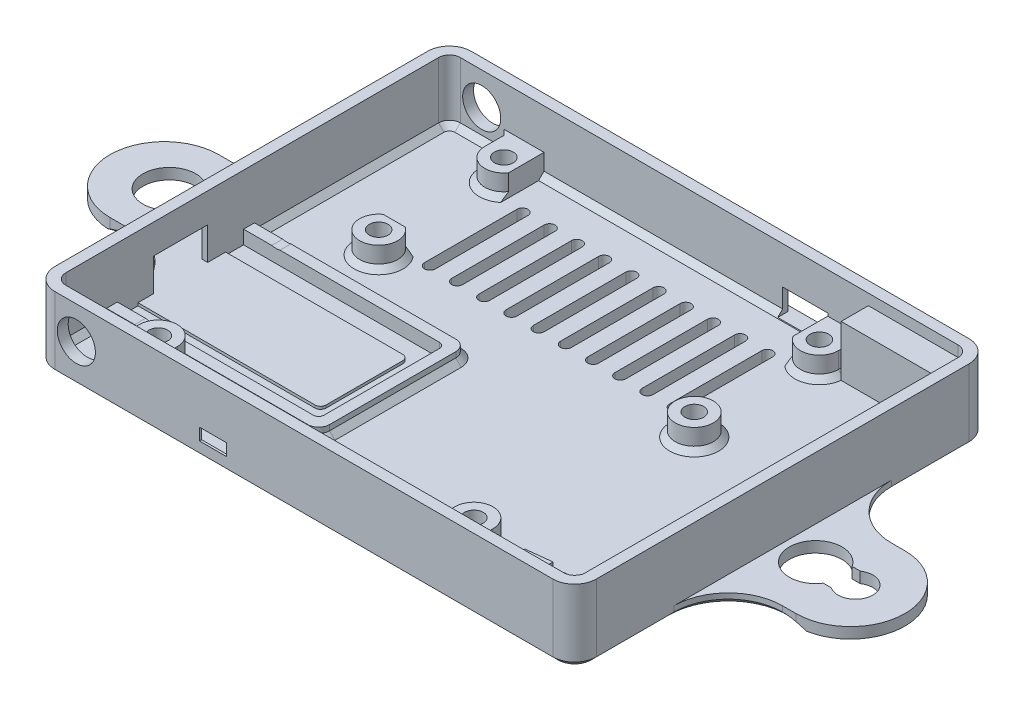
SolidWorks part; units mm, degrees
note: The reader was unsure of these and kept them because the rebuilt part matched: shared geometry of "Sketch2<3>".
ref_plane "Front Plane" through (0, 0, 0) normal (0, 0, 1) x (1, 0, 0)
ref_plane "Top Plane" through (0, 0, 0) normal (0, 1, 0) x (1, 0, 0)
ref_plane "Right Plane" through (0, 0, 0) normal (1, 0, 0) x (0, 0, -1)
sketch "Sketch1" plane through (0, 0, 0) normal (0, 1, 0) x (1, 0, 0)
  line L0 (-65.617, -16.3721) -> (-0.617, -16.3721)
  line L1 (-62.117, 10.1279) -> (-4.117, 10.1279)
  line L2 (-62.117, 10.1279) -> (-62.117, -12.8721)
  line L3 (-65.617, 13.6279) -> (-0.617, 13.6279)
  line L4 (-65.617, 13.6279) -> (-65.617, -16.3721)
  line L5 (-62.117, -12.8721) -> (-4.117, -12.8721)
  line L6 (-0.617, 13.6279) -> (-0.617, -16.3721)
  line L7 (-4.117, 10.1279) -> (-4.117, -12.8721)
  line L8 (-24.217, 16.7282) -> (-24.217, 15.4455)
  line L9 (-11.617, 16.7282) -> (-11.617, 15.4455)
  dimension "D1" = 65
  dimension "D2" = 30
  dimension "D3" = 58
  dimension "D4" = 23
  dimension "D5" = 3.5
  dimension "D6" = 3.5
sketch "Sketch2" plane through (0, 0, 0) normal (0, 1, 0) x (1, 0, 0)
  line L0 (-0.617, 13.6279) -> (-0.617, -16.3721) construction
  line L1 (32.4749, -18.9645) -> (30.9945, -18.9645)
  line L2 (32.4749, -24.2798) -> (30.9945, -24.2798)
  line L3 (33.3493, -21.6221) -> (26.04, -21.6221)
  line L4 (-85.4447, -21.6221) -> (-92.754, -21.6221)
  line L5 (-86.3191, -18.9645) -> (-87.7995, -18.9645)
  line L6 (-76.617, 13.6279) -> (-76.617, -16.3721)
  line L7 (-76.617, 12.6279) -> (-76.617, -55.8721)
  line L8 (-86.3191, -24.2798) -> (-87.7995, -24.2798)
  line L9 (-88.617, -11.6221) -> (-92.754, -11.6221)
  line L10 (-74.617, -57.8721) -> (16.883, -57.8721)
  line L11 (-78.617, -41.6221) -> (-78.617, -55.8721)
  line L12 (-88.617, -31.6221) -> (-92.754, -31.6221)
  line L13 (-85.4447, -11.6221) -> (-92.754, -11.6221) construction
  line L14 (18.883, 12.6279) -> (18.883, -55.8721)
  line L15 (-74.617, 14.6279) -> (16.883, 14.6279)
  line L16 (-74.617, -59.8721) -> (16.883, -59.8721)
  line L17 (20.883, 12.6279) -> (20.883, -1.6221)
  line L18 (-74.617, 16.6279) -> (16.883, 16.6279)
  line L19 (-85.4447, -31.6221) -> (-92.754, -31.6221) construction
  line L20 (33.3493, -11.6221) -> (30.883, -11.6221)
  line L21 (33.3493, -31.6221) -> (30.883, -31.6221)
  line L22 (33.3493, -11.6221) -> (26.04, -11.6221) construction
  line L23 (33.3493, -31.6221) -> (26.04, -31.6221) construction
  line L24 (-78.617, 12.6279) -> (-78.617, -55.8721) construction
  line L25 (-78.617, 12.6279) -> (-78.617, -1.6221)
  line L26 (20.883, 12.6279) -> (20.883, -55.8721) construction
  line L27 (20.883, -41.6221) -> (20.883, -55.8721)
  arc A0 (-74.617, -57.8721) -> (-76.617, -55.8721) centre (-74.617, -55.8721) cw
  arc A1 (16.883, -57.8721) -> (18.883, -55.8721) centre (16.883, -55.8721) ccw
  arc A2 (18.883, 12.6279) -> (16.883, 14.6279) centre (16.883, 12.6279) ccw
  arc A3 (-74.617, 14.6279) -> (-76.617, 12.6279) centre (-74.617, 12.6279) ccw
  arc A4 (-74.617, -59.8721) -> (-78.617, -55.8721) centre (-74.617, -55.8721) cw
  arc A5 (16.883, -59.8721) -> (20.883, -55.8721) centre (16.883, -55.8721) ccw
  arc A6 (20.883, 12.6279) -> (16.883, 16.6279) centre (16.883, 12.6279) ccw
  arc A7 (-74.617, 16.6279) -> (-78.617, 12.6279) centre (-74.617, 12.6279) ccw
  arc A8 (30.9945, -18.9645) -> (30.9945, -24.2798) centre (26.9479, -21.6221) ccw
  arc A9 (32.4749, -24.2798) -> (32.4749, -18.9645) centre (34.2572, -21.6221) ccw
  arc A10 (-86.3191, -24.2798) -> (-86.3191, -18.9645) centre (-84.5368, -21.6221) ccw
  arc A11 (-87.7995, -18.9645) -> (-87.7995, -24.2798) centre (-91.8461, -21.6221) ccw
  arc A12 (-92.754, -11.6221) -> (-92.754, -31.6221) centre (-92.754, -21.6221) ccw
  arc A13 (33.3493, -11.6221) -> (33.3493, -31.6221) centre (33.3493, -21.6221) cw
  arc A14 (-78.617, -41.6221) -> (-88.617, -31.6221) centre (-88.617, -41.6221) ccw
  arc A15 (-88.617, -11.6221) -> (-78.617, -1.6221) centre (-88.617, -1.6221) ccw
  arc A16 (20.883, -1.6221) -> (30.883, -11.6221) centre (30.883, -1.6221) ccw
  arc A17 (30.883, -31.6221) -> (20.883, -41.6221) centre (30.883, -41.6221) ccw
  point P62 (-78.617, -11.6221)
  point P67 (20.883, -31.6221)
  dimension "D4" = 2
  dimension "D10" = 10
  dimension "D11" = 10
  dimension "D12" = 10
  dimension "D13" = 10
  dimension "D3" = 72.5
  dimension "D2" = 19.5
  dimension "D1" = 11
  dimension "D5" = 2
  dimension "D6" = 10
  dimension "D7" = 10
  dimension "D8" = 10
  dimension "D9" = 10
extrude "Boss-Extrude1" add sketch "Sketch2" along normal blind 13.4 contours A17 L21 A13 L20 A16 L17 A6 L18 A7 L25 A15 L9 A12 L12 A14 L11 A4 L16 A5 L27 A11 L5 A10 L8 A9 L2 A8 L1 A3 L15 A2 L14 A1 L10 A0 L7
sketch "Sketch23" plane through (0, 13.4, 0) normal (0, 1, 0) x (1, 0, 0)
  line L1 (-78.617, -1.6221) -> (-103.7829, -1.6221)
  line L2 (-78.617, -1.6221) -> (-78.617, -41.6221)
  line L3 (-78.617, -41.6221) -> (-103.7829, -41.6221)
  line L4 (-103.7829, -1.6221) -> (-103.7829, -41.6221)
  line L5 (20.883, -1.6221) -> (47.1562, -1.6221)
  line L6 (20.883, -1.6221) -> (20.883, -41.6221)
  line L7 (20.883, -41.6221) -> (47.1562, -41.6221)
  line L8 (47.1562, -1.6221) -> (47.1562, -41.6221)
extrude "Cut-Extrude9" cut sketch "Sketch23" against normal offset from surface (11.4 mm away) 2 up to face at (-29.0341, 0, 21.6221)
extrude "Boss-Extrude2" add sketch "Sketch2<3>" along normal blind 2 contours L15 A3 L7 A0 L10 A1 L14 A2
sketch "Sketch2<3>" plane through (0, 0, 0) normal (0, 1, 0) x (1, 0, 0) same geometry as "Sketch2"
sketch "Sketch4" plane through (0, 2, 0) normal (0, 1, 0) x (1, 0, 0)
  line L0 (-59.2343, 14.6279) -> (-59.2343, 8.1428)
  line L5 (-7.0825, 14.6279) -> (-0.617, 14.6279)
  line L6 (-0.617, 10.1279) -> (-0.617, 14.6279)
  line L9 (-64.1397, -10.0158) -> (-60.0943, -10.0158)
  line L10 (-59.2343, 14.6279) -> (-65.617, 14.6279)
  line L11 (-65.617, 14.6279) -> (-65.617, 10.1279)
  line L12 (-7.0825, 14.6279) -> (-7.0825, 8.269)
  arc A1 (-7.0825, 8.269) -> (-0.617, 10.1279) centre (-4.117, 10.1279) ccw
  arc A2 (-64.1397, -10.0158) -> (-60.0943, -10.0158) centre (-62.117, -12.8721) ccw
  arc A3 (-65.617, 10.1279) -> (-59.2343, 8.1428) centre (-62.117, 10.1279) ccw
  circle A5 centre (-4.117, -12.8721) radius 3.5
extrude "Boss-Extrude3" add sketch "Sketch4" along normal offset from surface (4 mm away) 7.4 up to face at (-28.867, 13.4, 21.6221)
hole_wizard "CSK for #4 Flat Head Socket Cap Screw1" positions "Sketch6" profile "Sketch5" countersink size "#4" standard "ANSI Inch" end condition through all
sketch "Sketch6" plane through (0, 0, 0) normal (0, -1, 0) x (-1, 0, 0)
  point P0 (4.117, 10.1279)
  point P4 (62.117, 10.1279)
  point P8 (4.117, -12.8721)
  point P12 (62.117, -12.8721)
sketch "Sketch5" plane through (-4.117, 0, -10.1279) normal (1, 0, 0) x (0, 0, -1)
  line L0 (0, 0) -> (0, 13.4)
  line L1 (0, 13.4) -> (1.7272, 13.4)
  line L2 (1.7272, 13.4) -> (1.7272, 1.8805)
  line L3 (1.7272, 1.8805) -> (3.3619, 0)
  line L5 (3.3619, 0) -> (0, 0)
  line L6 (-1.7272, 1.8805) -> (-3.3619, 0) construction
  line L11 (0, -6.35) -> (0, 107.95) construction
  dimension "Thru Hole Dia." = 3.4544
  dimension "Thru Hole Depth" = 13.4
  dimension "Near C'Sink Dia." = 6.7237
  dimension "Near C'Sink Angle" = 82
sketch "Sketch7" plane through (0, 0, -16.6279) normal (0, 0, -1) x (-1, 0, 0)
  line L0 (11.2325, 6.5) -> (11.2325, 2.1) construction
  line L1 (7.0825, 6.5) -> (15.3825, 6.5)
  line L2 (7.0825, 6.5) -> (7.0825, 2.1)
  line L3 (7.0825, 2.1) -> (15.3825, 2.1)
  line L4 (15.3825, 6.5) -> (15.3825, 2.1)
  line L5 (0.617, 6) -> (7.0825, 6) construction
  dimension "D1" = 8.3
  dimension "D2" = 0.5
  dimension "D4" = 4.4
extrude "Cut-Extrude1" cut sketch "Sketch7" against normal up to next
sketch "Sketch15" plane through (0, 2, 0) normal (0, 1, 0) x (1, 0, 0)
  line L1 (-76.617, -23.2053) -> (-39.617, -23.2053)
  line L2 (-76.617, -21.2053) -> (-76.617, -23.2053)
  line L3 (-76.617, -46.4053) -> (-39.617, -46.4053)
  line L4 (-39.617, -23.2053) -> (-39.617, -46.4053)
  line L5 (-76.617, -21.2053) -> (-37.617, -21.2053)
  line L6 (-37.617, -21.2053) -> (-37.617, -48.4053)
  line L7 (-76.617, -48.4053) -> (-37.617, -48.4053)
  line L8 (-76.617, -46.4053) -> (-76.617, -48.4053)
  dimension "D1" = 23.2
extrude "Boss-Extrude5" add sketch "Sketch15" along normal blind 2
fillet "Fillet1" radius 1 1 edges at (-39.617, 3, 23.2053)
fillet "Fillet2" radius 1 1 edges at (-39.617, 3, 46.4053)
fillet "Fillet3" radius 2 2 edges at (-37.617, 3, 48.4053) (-37.617, 3, 21.2053)
sketch "Sketch16" plane through (-76.617, 0, 0) normal (1, 0, 0) x (0, 0, -1)
  line L1 (-39.8053, 2) -> (-29.8053, 2)
  line L2 (-39.8053, 2) -> (-39.8053, 8)
  line L3 (-39.8053, 8) -> (-29.8053, 8)
  line L4 (-29.8053, 2) -> (-29.8053, 8)
  dimension "D1" = 6
  dimension "D2" = 10
extrude "Cut-Extrude4" cut sketch "Sketch16" against normal up to next
sketch "Sketch9" plane through (0, 2, 0) normal (0, 1, 0) x (1, 0, 0)
  line L2 (-65.617, -57.8721) -> (-58.617, -57.8721)
  line L3 (-58.617, -53.3721) -> (-58.617, -57.8721)
  line L4 (-7.617, -53.3721) -> (-7.617, -57.8721)
  line L5 (-74.617, -57.8721) -> (16.883, -57.8721) construction
  line L6 (-65.617, -53.3721) -> (-65.617, -57.8721)
  line L7 (-7.617, -57.8721) -> (-0.617, -57.8721)
  line L8 (-0.617, -53.3721) -> (-0.617, -57.8721)
  arc A0 (-0.617, -53.3721) -> (-7.617, -53.3721) centre (-4.117, -53.3721) ccw
  arc A1 (-58.617, -53.3721) -> (-65.617, -53.3721) centre (-62.117, -53.3721) ccw
extrude "Boss-Extrude4" add sketch "Sketch9" along normal offset from surface (7.4 mm away) 4 up to face at (-28.867, 13.4, 21.6221)
hole_wizard "CSK for #4 Flat Head Socket Cap Screw2" positions "Sketch11" profile "Sketch10" countersink size "#4" standard "ANSI Inch" end condition through all
sketch "Sketch11" plane through (0, 0, 0) normal (0, -1, 0) x (-1, 0, 0)
  point P0 (4.117, -53.3721)
  point P9 (62.117, -53.3721)
sketch "Sketch10" plane through (-4.117, 0, 53.3721) normal (1, 0, 0) x (0, 0, -1)
  line L0 (0, 0) -> (0, 13.4)
  line L1 (0, 13.4) -> (1.7272, 13.4)
  line L2 (1.7272, 13.4) -> (1.7272, 1.8805)
  line L3 (1.7272, 1.8805) -> (3.3619, 0)
  line L5 (3.3619, 0) -> (0, 0)
  line L6 (-1.7272, 1.8805) -> (-3.3619, 0) construction
  line L11 (0, -6.35) -> (0, 107.95) construction
  dimension "Thru Hole Dia." = 3.4544
  dimension "Thru Hole Depth" = 13.4
  dimension "Near C'Sink Dia." = 6.7237
  dimension "Near C'Sink Angle" = 82
chamfer "Chamfer1" distance 1 angle 45 6 edges at (-65.617, 4, -14.6279) (-65.617, 5.7, 57.8721) (-58.617, 5.7, 57.8721) (-0.617, 4, -14.6279) (-0.617, 5.7, 57.8721) (-7.617, 5.7, 57.8721)
chamfer "Chamfer2" distance 1 angle 45 30 edges at (-62.117, 2, 16.3721) (-65.617, 2, -11.8779) (-63.1564, 2, -6.7858) (18.883, 2, 21.6221) (-70.617, 2, -14.6279) (-76.0312, 2, -14.0421) (-76.617, 2, 4.2887) (-33.1584, 2, -14.6279) (-70.617, 2, 57.8721) (-76.0312, 2, 57.2864) (-65.617, 2, 55.1221) (-62.117, 2, 49.8721) (-58.617, 2, 55.1221) (8.633, 2, 57.8721) (18.2972, 2, 57.2864) (-33.117, 2, 57.8721) (8.633, 2, -14.6279) (18.2972, 2, -14.0421) (-0.617, 2, -11.8779) (-3.1499, 2, -6.7641) (-0.617, 2, 55.1221) (-7.617, 2, 55.1221) (-4.117, 2, 49.8721) (-4.117, 2, 16.3721) (-58.117, 2, 48.4053) (-58.117, 2, 21.2053) (-38.2028, 2, 47.8195) (-38.2028, 2, 21.791) (-37.617, 2, 34.8053) (-76.617, 2, 52.1387)
chamfer "Chamfer3" distance 1 angle 45 7 edges at (19.7114, 0, 58.7006) (-77.4454, 0, 58.7006) (-78.617, 0, 48.7471) (19.7114, 0, -15.4563) (-78.617, 0, -5.5029) (-77.4454, 0, -15.4563) (-28.867, 0, -16.6279)
chamfer "Chamfer4" distance 1 angle 45 4 edges at (-15.3825, 4.3, -16.6279) (-7.0825, 4.3, -16.6279) (-78.617, 5, 39.8053) (-78.617, 5, 29.8053)
sketch "Sketch12" plane through (0, 0, 0) normal (0, -1, 0) x (1, 0, 0)
  line L0 (-55.6605, 9.9113) -> (-55.6605, -7.0887) construction
  line L1 (-54.6605, 9.9113) -> (-54.6605, -7.0887)
  line L2 (-56.6605, 9.9113) -> (-56.6605, -7.0887)
  line L3 (-50.6605, 9.9113) -> (-50.6605, -7.0887) construction
  line L4 (-49.6605, 9.9113) -> (-49.6605, -7.0887)
  line L5 (-51.6605, 9.9113) -> (-51.6605, -7.0887)
  line L6 (-45.6605, 9.9113) -> (-45.6605, -7.0887) construction
  line L7 (-44.6605, 9.9113) -> (-44.6605, -7.0887)
  line L8 (-46.6605, 9.9113) -> (-46.6605, -7.0887)
  line L9 (-40.6605, 9.9113) -> (-40.6605, -7.0887) construction
  line L10 (-39.6605, 9.9113) -> (-39.6605, -7.0887)
  line L11 (-41.6605, 9.9113) -> (-41.6605, -7.0887)
  line L12 (-35.6605, 9.9113) -> (-35.6605, -7.0887) construction
  line L13 (-34.6605, 9.9113) -> (-34.6605, -7.0887)
  line L14 (-36.6605, 9.9113) -> (-36.6605, -7.0887)
  line L15 (-30.6605, 9.9113) -> (-30.6605, -7.0887) construction
  line L16 (-29.6605, 9.9113) -> (-29.6605, -7.0887)
  line L17 (-31.6605, 9.9113) -> (-31.6605, -7.0887)
  line L18 (-25.6605, 9.9113) -> (-25.6605, -7.0887) construction
  line L19 (-24.6605, 9.9113) -> (-24.6605, -7.0887)
  line L20 (-26.6605, 9.9113) -> (-26.6605, -7.0887)
  line L21 (-20.6605, 9.9113) -> (-20.6605, -7.0887) construction
  line L22 (-19.6605, 9.9113) -> (-19.6605, -7.0887)
  line L23 (-21.6605, 9.9113) -> (-21.6605, -7.0887)
  line L24 (-15.6605, 9.9113) -> (-15.6605, -7.0887) construction
  line L25 (-14.6605, 9.9113) -> (-14.6605, -7.0887)
  line L26 (-16.6605, 9.9113) -> (-16.6605, -7.0887)
  line L27 (-10.6605, 9.9113) -> (-10.6605, -7.0887) construction
  line L28 (-9.6605, 9.9113) -> (-9.6605, -7.0887)
  line L29 (-11.6605, 9.9113) -> (-11.6605, -7.0887)
  arc A0 (-54.6605, 9.9113) -> (-56.6605, 9.9113) centre (-55.6605, 9.9113) ccw
  arc A1 (-56.6605, -7.0887) -> (-54.6605, -7.0887) centre (-55.6605, -7.0887) ccw
  arc A2 (-49.6605, 9.9113) -> (-51.6605, 9.9113) centre (-50.6605, 9.9113) ccw
  arc A3 (-51.6605, -7.0887) -> (-49.6605, -7.0887) centre (-50.6605, -7.0887) ccw
  arc A4 (-44.6605, 9.9113) -> (-46.6605, 9.9113) centre (-45.6605, 9.9113) ccw
  arc A5 (-46.6605, -7.0887) -> (-44.6605, -7.0887) centre (-45.6605, -7.0887) ccw
  arc A6 (-39.6605, 9.9113) -> (-41.6605, 9.9113) centre (-40.6605, 9.9113) ccw
  arc A7 (-41.6605, -7.0887) -> (-39.6605, -7.0887) centre (-40.6605, -7.0887) ccw
  arc A8 (-34.6605, 9.9113) -> (-36.6605, 9.9113) centre (-35.6605, 9.9113) ccw
  arc A9 (-36.6605, -7.0887) -> (-34.6605, -7.0887) centre (-35.6605, -7.0887) ccw
  arc A10 (-29.6605, 9.9113) -> (-31.6605, 9.9113) centre (-30.6605, 9.9113) ccw
  arc A11 (-31.6605, -7.0887) -> (-29.6605, -7.0887) centre (-30.6605, -7.0887) ccw
  arc A12 (-24.6605, 9.9113) -> (-26.6605, 9.9113) centre (-25.6605, 9.9113) ccw
  arc A13 (-26.6605, -7.0887) -> (-24.6605, -7.0887) centre (-25.6605, -7.0887) ccw
  arc A14 (-19.6605, 9.9113) -> (-21.6605, 9.9113) centre (-20.6605, 9.9113) ccw
  arc A15 (-21.6605, -7.0887) -> (-19.6605, -7.0887) centre (-20.6605, -7.0887) ccw
  arc A16 (-14.6605, 9.9113) -> (-16.6605, 9.9113) centre (-15.6605, 9.9113) ccw
  arc A17 (-16.6605, -7.0887) -> (-14.6605, -7.0887) centre (-15.6605, -7.0887) ccw
  arc A18 (-9.6605, 9.9113) -> (-11.6605, 9.9113) centre (-10.6605, 9.9113) ccw
  arc A19 (-11.6605, -7.0887) -> (-9.6605, -7.0887) centre (-10.6605, -7.0887) ccw
  point P2 (-55.6605, 1.4113)
  point P10 (-50.6605, 1.4113)
  point P17 (-45.6605, 1.4113)
  point P24 (-40.6605, 1.4113)
  point P31 (-35.6605, 1.4113)
  point P38 (-30.6605, 1.4113)
  point P45 (-25.6605, 1.4113)
  point P52 (-20.6605, 1.4113)
  point P59 (-15.6605, 1.4113)
  point P66 (-10.6605, 1.4113)
  dimension "D1" = 2
  dimension "D2" = 17
  dimension "D3" = 10
extrude "Cut-Extrude2" cut sketch "Sketch12" against normal up to next
sketch "Sketch14" plane through (0, 0, 59.8721) normal (0, 0, 1) x (1, 0, 0)
  circle A0 centre (-70.6879, 7.4174) radius 3.5
extrude "Cut-Extrude3" cut sketch "Sketch14" against normal through all
sketch "Sketch17" plane through (0, 2, 0) normal (0, 1, 0) x (1, 0, 0)
  line L0 (11.4337, -55.3721) -> (18.883, -55.3721)
  line L1 (-0.617, -56.8721) -> (-0.617, -53.3721) construction
  line L2 (-0.617, -56.3721) -> (18.883, -56.3721)
  line L3 (-0.617, -56.3721) -> (-0.617, -55.3721)
  line L4 (-0.617, -55.3721) -> (6.2301, -55.3721)
  line L6 (18.883, -56.3721) -> (18.883, -55.3721)
  line L9 (16.883, -57.8721) -> (0.383, -57.8721) construction
  line L12 (6.2301, -55.3721) -> (6.2301, -54.3721)
  line L13 (6.2301, -54.3721) -> (11.4337, -54.3721)
  line L14 (11.4337, -55.3721) -> (11.4337, -54.3721)
  dimension "D1" = 1
  dimension "D2" = 1.5
  dimension "D3" = 1
extrude "Boss-Extrude6" add sketch "Sketch17" along normal up to vertex (11.4 mm away)
sketch "Sketch18" plane through (0, 0, 54.3721) normal (0, 0, -1) x (-1, 0, 0)
  line L0 (-0.383, 6) -> (-18.883, 6)
  line L1 (-18.883, 13.4) -> (-18.883, 3) construction
  line L2 (-18.883, 6) -> (-18.883, 3)
  line L3 (-18.883, 3) -> (-17.749, 2)
  line L4 (-17.749, 2) -> (-0.383, 2)
  line L5 (-0.383, 2) -> (0.617, 3)
  line L6 (0.617, 3) -> (0.617, 6)
  line L7 (0.617, 9.4) -> (0.617, 13.4)
  line L8 (0.617, 13.4) -> (-18.883, 13.4)
  line L9 (-18.883, 13.4) -> (-18.883, 11.4)
  line L10 (-18.883, 11.4) -> (0.617, 9.4)
  line L11 (-0.383, 6) -> (0.617, 6)
extrude "Cut-Extrude5" cut sketch "Sketch18" against normal up to vertex
sketch "Sketch19" plane through (-134.4891, 0, 57.8721) normal (0, 0, -1) x (-1, 0, 0)
  line L1 (-94.8286, 6) -> (-83.0286, 6)
  line L2 (-94.8286, 6) -> (-94.8286, 2)
  line L3 (-94.8286, 2) -> (-83.0286, 2)
  line L4 (-83.0286, 6) -> (-83.0286, 2)
  dimension "D1" = 4
  dimension "D2" = 11.8
extrude "Cut-Extrude6" cut sketch "Sketch19" against normal offset from surface 0.4 and the other way blind 2 up to face at (-67.1879, 7.4174, 59.8721)
sketch "Sketch20" plane through (0, 0, 59.4721) normal (0, 0, -1) x (-1, 0, 0)
  line L0 (39.6605, 4) -> (51.4605, 4) construction
  line L3 (45.5605, 6) -> (45.5605, 2) construction
  line L7 (43.0605, 2.9) -> (48.0605, 2.9)
  line L8 (43.0605, 2.9) -> (43.0605, 5.1)
  line L9 (43.0605, 5.1) -> (48.0605, 5.1)
  line L10 (48.0605, 2.9) -> (48.0605, 5.1)
  line L11 (43.0605, 2.9) -> (48.0605, 5.1) construction
  line L12 (43.0605, 5.1) -> (48.0605, 2.9) construction
  point P12 (45.5605, 4)
  dimension "D1" = 5
  dimension "D2" = 2.2
extrude "Cut-Extrude7" cut sketch "Sketch20" against normal through all
sketch "Sketch21" plane through (0, 2, 0) normal (0, 1, 0) x (1, 0, 0)
  line L0 (-76.617, -23.2053) -> (-76.617, -29.8053) construction
  line L1 (-76.617, -26.5053) -> (-44.0563, -26.5053)
  line L3 (-76.617, -42.6194) -> (-44.0563, -42.6194)
  line L4 (-43.0563, -27.5053) -> (-43.0563, -41.6194)
  line L5 (-76.617, -42.6194) -> (-76.617, -46.4053)
  line L6 (-76.617, -23.2053) -> (-40.617, -23.2053)
  line L7 (-76.617, -23.2053) -> (-76.617, -26.5053)
  line L8 (-76.617, -46.4053) -> (-40.617, -46.4053)
  line L9 (-39.617, -24.2053) -> (-39.617, -45.4053)
  arc A0 (-43.0563, -27.5053) -> (-44.0563, -26.5053) centre (-44.0563, -27.5053) ccw
  arc A1 (-44.0563, -42.6194) -> (-43.0563, -41.6194) centre (-44.0563, -41.6194) ccw
  arc A2 (-39.617, -45.4053) -> (-40.617, -46.4053) centre (-40.617, -45.4053) cw
  arc A3 (-39.617, -24.2053) -> (-40.617, -23.2053) centre (-40.617, -24.2053) ccw
  dimension "D1" = 1
extrude "Cut-Extrude8" cut sketch "Sketch21" against normal blind 0.5
sketch "Sketch22" plane through (0, 0, 57.8721) normal (0, 0, -1) x (-1, 0, 0)
  line L0 (38.1605, 7.5) -> (38.1605, 2)
  line L1 (39.6605, 6) -> (51.4605, 6)
  line L2 (39.6605, 6) -> (39.6605, 2)
  line L3 (52.9605, 7.5) -> (52.9605, 0.5) construction
  line L4 (51.4605, 6) -> (51.4605, 2)
  line L6 (52.9605, 7.5) -> (52.9605, 2)
  line L7 (38.1605, 7.5) -> (52.9605, 7.5)
  line L8 (39.6605, 2) -> (38.1605, 2)
  line L9 (7.0825, 2) -> (59.2343, 2) construction
  line L10 (51.4605, 2) -> (52.9605, 2)
  line L11 (38.1605, 7.5) -> (38.1605, 0.5) construction
  line L12 (38.1605, 0.5) -> (52.9605, 0.5) construction
  line L13 (39.6605, 2) -> (51.4605, 2) construction
  dimension "D1" = 1.5
extrude "Boss-Extrude7" add sketch "Sketch22" along normal blind 2
sketch "Sketch24" plane through (0, 0, -14.6279) normal (0, 0, 1) x (1, 0, 0)
  line L1 (18.883, 11.4) -> (0.383, 11.4)
  line L2 (18.883, 11.4) -> (18.883, 2)
  line L3 (18.883, 2) -> (0.383, 2)
  line L4 (0.383, 11.4) -> (0.383, 2)
extrude "Boss-Extrude8" add sketch "Sketch24" along normal blind 5
